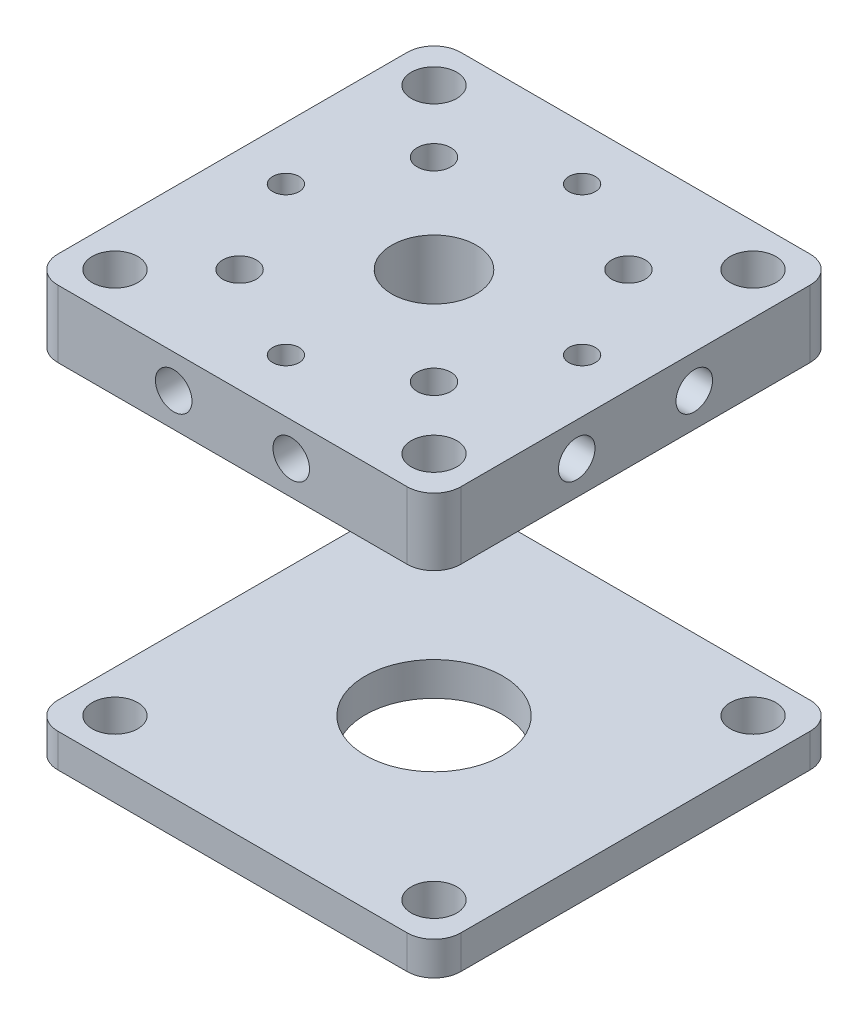
SolidWorks part; units mm, degrees
material "Alum Plate"
ref_plane "Front Plane" through (0, 0, 0) normal (0, 0, 1) x (1, 0, 0)
ref_plane "Top Plane" through (0, 0, 0) normal (0, 1, 0) x (1, 0, 0)
ref_plane "Right Plane" through (0, 0, 0) normal (1, 0, 0) x (0, 0, -1)
other "Bounding Box"
ref_plane "Default Plane" through (-8.9266, -12.7485, 0) normal (-0.1736, 0.9848, 0) x (0.9848, 0.1736, 0)
sketch "Sketch1" plane through (0, 0, 0) normal (0, 1, 0) x (1, 0, 0)
  line L0 (0, -12.5) -> (0, 12.5) construction
  line L1 (-14, 0) -> (0, 14) construction
  line L2 (-19.05, 19.05) -> (19.05, 19.05)
  line L3 (-19.05, 19.05) -> (-19.05, -19.05)
  line L4 (-19.05, -19.05) -> (19.05, -19.05)
  line L5 (19.05, 19.05) -> (19.05, -19.05)
  line L6 (-19.05, 19.05) -> (19.05, -19.05) construction
  line L7 (-19.05, -19.05) -> (19.05, 19.05) construction
  line L8 (9.1924, 9.1924) -> (-9.1924, 9.1924) construction
  line L9 (9.1924, 9.1924) -> (9.1924, -9.1924) construction
  line L10 (9.1924, -9.1924) -> (-9.1924, -9.1924) construction
  line L11 (-9.1924, 9.1924) -> (-9.1924, -9.1924) construction
  line L12 (9.1924, 9.1924) -> (-9.1924, -9.1924) construction
  line L13 (9.1924, -9.1924) -> (-9.1924, 9.1924) construction
  line L14 (-14, 0) -> (0, -14) construction
  line L15 (0, 14) -> (14, 0) construction
  line L16 (0, -14) -> (14, 0) construction
  line L17 (-14, 0) -> (14, 0) construction
  line L18 (0, 14) -> (0, -14) construction
  circle A0 centre (-15.24, 15.24) radius 1.3843 construction
  circle A1 centre (15.24, 15.24) radius 1.3843 construction
  circle A2 centre (15.24, -15.24) radius 1.3843 construction
  circle A3 centre (-15.24, -15.24) radius 1.3843 construction
  circle A4 centre (0, 0) radius 4
  circle A5 centre (9.1924, 9.1924) radius 1.5875
  circle A6 centre (9.1924, -9.1924) radius 1.5875
  circle A7 centre (-9.1924, -9.1924) radius 1.5875
  circle A8 centre (-9.1924, 9.1924) radius 1.5875
  circle A9 centre (-14, 0) radius 1.25
  circle A10 centre (0, 14) radius 1.25
  circle A11 centre (14, 0) radius 1.25
  circle A12 centre (0, -14) radius 1.25
  arc A13 (-9.8995, 9.8995) -> (0, 14) centre (0, 0) cw
  point P3 (0, 0)
  circle B0 centre (-9.8995, -9.8995) radius 1.2645 construction
  circle B1 centre (0, -8) radius 1.5875 construction
  circle B2 centre (0, 0) radius 4 construction
  circle B3 centre (9.8995, 9.8995) radius 1.2645 construction
  circle B4 centre (0, 8) radius 1.5875 construction
  circle B5 centre (9.8995, -9.8995) radius 1.2645 construction
  circle B6 centre (0, -12.5) radius 1.5875 construction
  circle B7 centre (-9.5, 0) radius 1.5875 construction
  circle B8 centre (-15.24, 15.24) radius 1.3843 construction
  circle B9 centre (15.24, 15.24) radius 1.3843 construction
  circle B10 centre (15.24, -15.24) radius 1.3843 construction
  circle B11 centre (-15.24, -15.24) radius 1.3843 construction
  circle B12 centre (9.5, 0) radius 1.5875 construction
  circle B13 centre (-9.8995, 9.8995) radius 1.2645 construction
  circle B14 centre (0, 12.5) radius 1.5875 construction
  dimension "D2" = 3.175
  dimension "D4" = 2.5
  dimension "D1" = 38.1
  dimension "D3" = 26
sketch_block_instance "Block-36mm gearbox motor block holes-1"
sketch_block "Block-36mm gearbox motor block holes"
extrude "Boss-Extrude1" add sketch "Sketch1" along normal mid plane 6.35 contours L5 L2 L3 L4 A12 A11 A9 A8 A10 A7 A6 A5 A4 A3 A2 A1 A0 region at (0, 0, -18.5112)
sketch "Sketch4" plane through (0, 0, 19.05) normal (0, 0, 1) x (1, 0, 0)
  line L0 (-5.5562, 0) -> (0, 0) construction
  line L1 (0, 0) -> (5.5562, 0) construction
  circle A0 centre (-5.5562, 0) radius 1.7272
  circle A1 centre (5.5562, 0) radius 1.7272
  dimension "D2" = 3.4544
  dimension "D1" = 11.1125
extrude "Cut-Extrude2" cut sketch "Sketch4" against normal blind 9.525
sketch "Sketch7" plane through (0, -3.175, 0) normal (0, -1, 0) x (1, 0, 0)
  line L0 (-19.05, 15.0813) -> (-15.0813, 15.0813) construction
  line L1 (-19.05, -19.05) -> (-19.05, 19.05) construction
  line L2 (-15.0813, 15.0813) -> (-15.0813, 19.05) construction
  line L3 (-19.05, 19.05) -> (19.05, 19.05) construction
  line L4 (0, 0) -> (-15.0813, 15.0813) construction
  line L5 (0, 0) -> (15.0813, 15.0812) construction
  circle A0 centre (-15.0813, 15.0813) radius 2.1526
  circle A1 centre (15.0813, 15.0812) radius 2.1527
  circle A2 centre (15.0812, -15.0813) radius 2.1527
  circle A3 centre (-15.0813, -15.0812) radius 2.1526
  dimension "D2" = 4.3053
  dimension "D1" = 3.9688
  dimension "D4" = 90
  dimension "D3" = 4
extrude "Cut-Extrude3" cut sketch "Sketch7" against normal through all
pattern_circular "CirPattern1" count 4 over 360 about axis through (0, 3.175, 0) along (0, -1, 0) of "Cut-Extrude2"
ref_plane "Plane1" through (0, -33.3502, 0) normal (0, -1, 0) x (-1, 0, 0)
sketch "Sketch6" plane through (0, -33.3502, 0) normal (0, -1, 0) x (-1, 0, 0)
  line L0 (19.05, 19.05) -> (-19.05, 19.05) construction
  line L1 (19.05, 19.05) -> (19.05, -19.05) construction
  line L2 (19.05, -19.05) -> (-19.05, -19.05) construction
  line L3 (-19.05, 19.05) -> (-19.05, -19.05) construction
  line L12 (19.05, 19.05) -> (-19.05, 19.05)
  line L13 (19.05, 19.05) -> (19.05, -19.05)
  line L14 (19.05, -19.05) -> (-19.05, -19.05)
  line L15 (-19.05, 19.05) -> (-19.05, -19.05)
  circle A8 centre (0, 0) radius 6.5
  circle A17 centre (-15.0812, 15.0813) radius 2.1526
  circle A18 centre (15.0813, 15.0812) radius 2.1526
  circle A19 centre (15.0813, -15.0813) radius 2.1527
  circle A20 centre (-15.0813, -15.0812) radius 2.1526
  circle A21 centre (-15.0812, 15.0813) radius 2.1527 construction
  dimension "D2" = 13
extrude "Boss-Extrude2" add sketch "Sketch6" along normal blind 3.175 separate body
fillet "Fillet1" radius 2.54 4 edges at (-19.05, 0, 19.05) (-19.05, 0, -19.05) (19.05, 0, -19.05) (19.05, 0, 19.05)
fillet "Fillet2" radius 2.54 4 edges at (-19.05, -34.9377, 19.05) (-19.05, -34.9377, -19.05) (19.05, -34.9377, -19.05) (19.05, -34.9377, 19.05)
